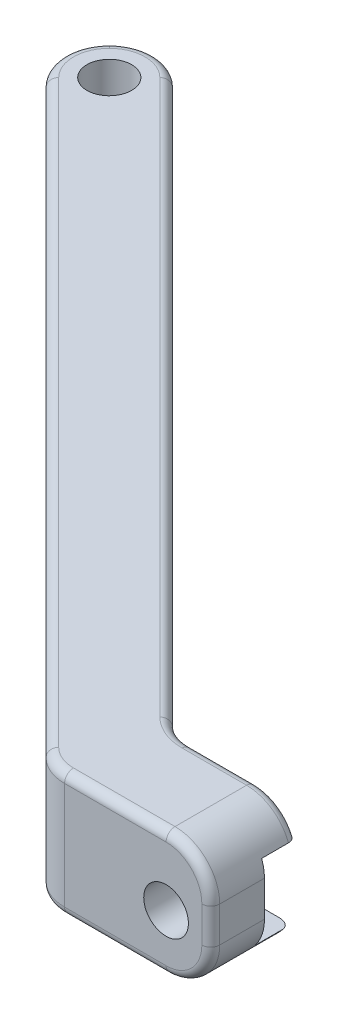
SolidWorks part; units mm, degrees
ref_plane "Front Plane" through (0, 0, 0) normal (0, 0, 1) x (1, 0, 0)
ref_plane "Top Plane" through (0, 0, 0) normal (0, 1, 0) x (1, 0, 0)
ref_plane "Right Plane" through (0, 0, 0) normal (1, 0, 0) x (0, 0, -1)
sketch "Sketch1" plane through (0, 0, 0) normal (0, 1, 0) x (1, 0, 0)
  line L0 (0, 7.0711) -> (-7.0711, 0)
  line L1 (0, 7.0711) -> (66.9211, -59.85)
  line L2 (-7.0711, 0) -> (62.7789, -69.85)
  line L4 (66.9211, -59.85) -> (81.2, -59.85)
  line L5 (81.2, -59.85) -> (81.2, -69.85)
  line L6 (81.2, -69.85) -> (62.7789, -69.85)
  circle A0 centre (0, 0) radius 2.5
  point P6 (76.2, -63.5)
  dimension "D1" = 5
  dimension "D2" = 5
  dimension "D3" = 5
  dimension "D4" = 10
  dimension "D5" = 69.85
  dimension "D6" = 45
  dimension "D7" = 10
  dimension "D8" = 5
  dimension "D9" = 76.2
  dimension "D10" = 63.5
extrude "Boss-Extrude1" add sketch "Sketch1" along normal blind 13.97
sketch "Sketch2" plane through (0, 0, 59.85) normal (0, 0, -1) x (-1, 0, 0)
  line L0 (-81.2, 13.97) -> (-81.2, 0) construction
  line L1 (-81.2, 0) -> (-66.9211, 0) construction
  circle A0 centre (-76.2, 6.35) radius 2.5
  dimension "D1" = 5
  dimension "D2" = 5
  dimension "D3" = 6.35
extrude "Cut-Extrude1" cut sketch "Sketch2" against normal up to next
fillet "Fillet1" radius 5 6 edges at (-7.0711, 6.985, 0) (0, 6.985, -7.0711) (81.2, 0, 64.85) (81.2, 13.97, 64.85) (62.7789, 6.985, 69.85) (66.9211, 6.985, 59.85)
fillet "Fillet2" radius 1 22 edges at (-5, 13.97, 0) (0, 13.97, -5) (34.4961, 13.97, 27.425) (67.0787, 13.97, 59.4694) (72.5961, 13.97, 59.85) (79.7355, 12.5055, 59.85) (81.2, 6.985, 59.85) (79.7355, 1.4645, 59.85) (72.5961, 0, 59.85) (67.0787, 0, 59.4694) (34.4961, 0, 27.425) (0, 0, -5) (-5, 0, 0) (28.8895, 0, 35.9605) (62.9366, 0, 69.4694) (70.525, 0, 69.85) (79.7355, 1.4645, 69.85) (81.2, 6.985, 69.85) (79.7355, 12.5055, 69.85) (70.525, 13.97, 69.85) (62.9366, 13.97, 69.4694) (28.8895, 13.97, 35.9605)
sketch "Sketch3" plane through (0, 0, 59.85) normal (0, 0, -1) x (-1, 0, 0)
  line L0 (-78.7259, 1.975) -> (-82.609, 1.975)
  line L1 (-73.6741, 1.975) -> (-71.1482, 6.35)
  line L2 (-71.1482, 6.35) -> (-73.6741, 10.725)
  line L3 (-73.6741, 10.725) -> (-78.7259, 10.725)
  line L4 (-78.7259, 10.725) -> (-81.2518, 6.35)
  line L5 (-81.2518, 6.35) -> (-78.7259, 1.975)
  line L6 (-78.7259, 1.975) -> (-73.6741, 1.975)
  line L7 (-82.609, 1.975) -> (-82.609, 10.725)
  line L8 (-82.609, 10.725) -> (-78.7259, 10.725)
  circle A0 centre (-76.2, 6.35) radius 4.375 construction
  circle M7 centre (-76.2, 6.35) radius 2.5
  arc M10 (-76.2, 12.97) -> (-80.2, 8.97) centre (-76.2, 8.97) ccw
  line M11 (-80.2, 8.97) -> (-80.2, 5)
  arc M12 (-80.2, 5) -> (-76.2, 1) centre (-76.2, 5) ccw
  dimension "D1" = 8.75
extrude "Cut-Extrude2" cut sketch "Sketch3" against normal blind 4 contours L5 L6 L1 L2 L3 L4 M11 M12 M7 | L8 L7 L0 L5 L4 M12 M11 M10 | L4 L5 M12 M11 | L8 L4 M10 M11 | L5 L0 M12 region at (79.5171, 3.1026, 59.85) region at (79.336, 3.2836, 59.85) region at (81.3697, 6.1687, 59.85) region at (80.5496, 6.3453, 59.85) region at (79.6564, 9.8152, 59.85)
